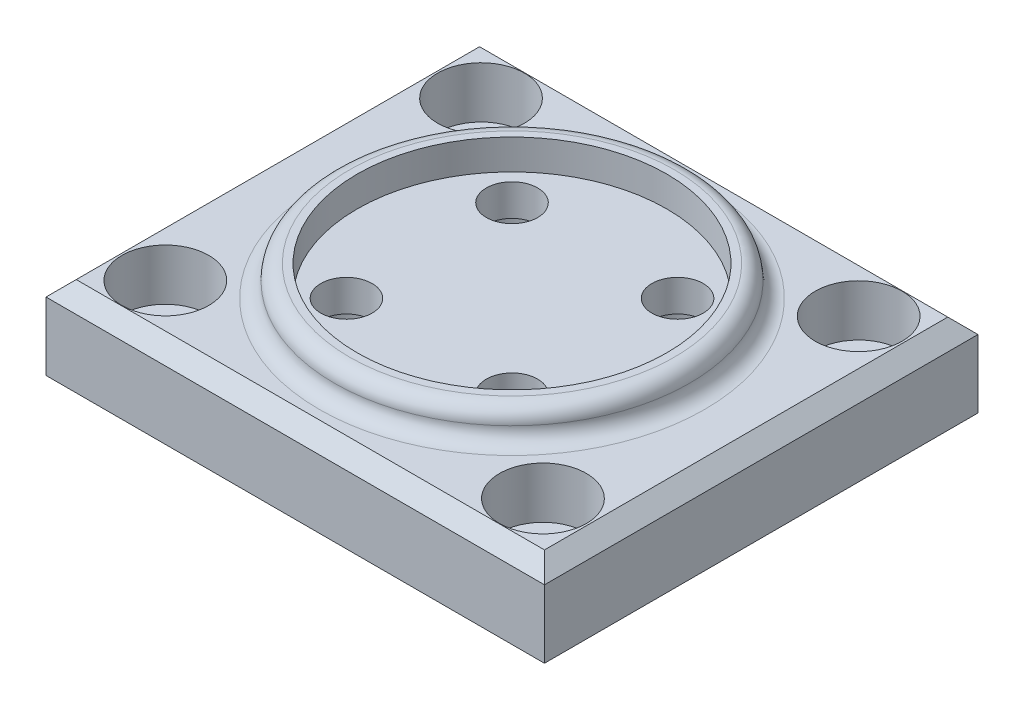
SolidWorks part; units mm, degrees
ref_plane "Front Plane" through (0, 0, 0) normal (0, 0, 1) x (1, 0, 0)
ref_plane "Top Plane" through (0, 0, 0) normal (0, 1, 0) x (1, 0, 0)
ref_plane "Right Plane" through (0, 0, 0) normal (1, 0, 0) x (0, 0, -1)
sketch "Sketch1" plane through (0, 0, 0) normal (0, 1, 0) x (1, 0, 0)
  line L1 (16.5, -14.35) -> (-16.5, -14.35)
  line L2 (16.5, -14.35) -> (16.5, 14.35)
  line L3 (16.5, 14.35) -> (-16.5, 14.35)
  line L4 (-16.5, -14.35) -> (-16.5, 14.35)
  line L5 (16.5, -14.35) -> (-16.5, 14.35) construction
  line L6 (16.5, 14.35) -> (-16.5, -14.35) construction
  point P0 (0, 0)
  dimension "D1" = 28.7
  dimension "D2" = 33
extrude "Boss-Extrude1" add sketch "Sketch1" along normal blind 5.5
hole_wizard "CBORE for M3 SHCS1" positions "Sketch3" profile "Sketch4" counterbore size "M3" standard "ANSI Metric"
sketch "Sketch3" plane through (0, 5.5, 0) normal (0, 1, 0) x (1, 0, 0)
  line L1 (12.5, -10.45) -> (-12.5, -10.45)
  line L2 (12.5, -10.45) -> (12.5, 10.45)
  line L3 (12.5, 10.45) -> (-12.5, 10.45)
  line L4 (-12.5, -10.45) -> (-12.5, 10.45)
  line L5 (12.5, -10.45) -> (-12.5, 10.45) construction
  line L6 (12.5, 10.45) -> (-12.5, -10.45) construction
  point P0 (-12.5, 10.45)
  point P2 (12.5, 10.45)
  point P4 (12.5, -10.45)
  point P6 (-12.5, -10.45)
  point P9 (0, 0)
  dimension "D1" = 20.9
  dimension "D2" = 25
sketch "Sketch4" plane through (-12.5, 5.5, -10.45) normal (1, 0, 0) x (0, 0, 1)
  line L0 (0, 0) -> (0, 5.5)
  line L1 (0, 5.5) -> (1.7, 5.5)
  line L3 (1.7, 5.5) -> (1.7, 3.4)
  line L4 (1.7, 3.4) -> (2.875, 3.4)
  line L5 (2.875, 3.4) -> (2.875, 0)
  line L7 (2.875, 0) -> (0, 0)
  line L11 (0, -6.35) -> (0, 107.95) construction
  dimension "Thru Hole Dia." = 3.4
  dimension "Thru Hole Depth" = 5.5
  dimension "C'Bore Dia." = 5.75
  dimension "C'Bore Depth" = 3.4
sketch "Sketch5" plane through (0, 0, 0) normal (0, 1, 0) x (1, 0, 0)
  circle A0 centre (0, 0) radius 10
  dimension "D1" = 20
sketch "Sketch7" plane through (0, 0, 0) normal (0, -1, 0) x (-1, 0, 0)
  line L1 (5.4801, 5.4801) -> (-5.4801, 5.4801)
  line L2 (5.4801, 5.4801) -> (5.4801, -5.4801)
  line L3 (5.4801, -5.4801) -> (-5.4801, -5.4801)
  line L4 (-5.4801, 5.4801) -> (-5.4801, -5.4801)
  line L5 (5.4801, 5.4801) -> (-5.4801, -5.4801) construction
  line L6 (5.4801, -5.4801) -> (-5.4801, 5.4801) construction
  circle A2 centre (0, 0) radius 7.75
  point P0 (-5.4801, -5.4801)
  point P2 (5.4801, -5.4801)
  point P4 (5.4801, 5.4801)
  point P6 (-5.4801, 5.4801)
  dimension "D3" = 15.5
hole_wizard "CBORE for M3 SHCS2" positions "Sketch7" profile "Sketch8" counterbore size "M3" standard "ANSI Metric" end condition through all
sketch "Sketch8" plane through (5.4801, 0, 5.4801) normal (1, 0, 0) x (0, 0, -1)
  line L0 (0, 0) -> (0, 5.5)
  line L1 (0, 5.5) -> (1.7, 5.5)
  line L3 (1.7, 5.5) -> (1.7, 3.4)
  line L4 (1.7, 3.4) -> (2.875, 3.4)
  line L5 (2.875, 3.4) -> (2.875, 0)
  line L7 (2.875, 0) -> (0, 0)
  line L11 (0, -6.35) -> (0, 107.95) construction
  dimension "Thru Hole Dia." = 3.4
  dimension "Thru Hole Depth" = 5.5
  dimension "C'Bore Dia." = 5.75
  dimension "C'Bore Depth" = 3.4
sketch "Sketch9" plane through (0, 5.5, 0) normal (0, 1, 0) x (1, 0, 0)
  circle A0 centre (0, 0) radius 11.75
  circle A1 centre (0, 0) radius 10.25
  dimension "D1" = 20.5
  dimension "D2" = 23.5
extrude "Boss-Extrude2" add sketch "Sketch9" along normal blind 2
fillet "Fillet1" radius 1 2 edges at (0, 7.5, 11.75) (0, 5.5, 11.75)
chamfer "Chamfer1" distance 1 angle 45 4 edges at (16.5, 5.5, 0) (0, 5.5, -14.35) (-16.5, 5.5, 0) (0, 5.5, 14.35)
